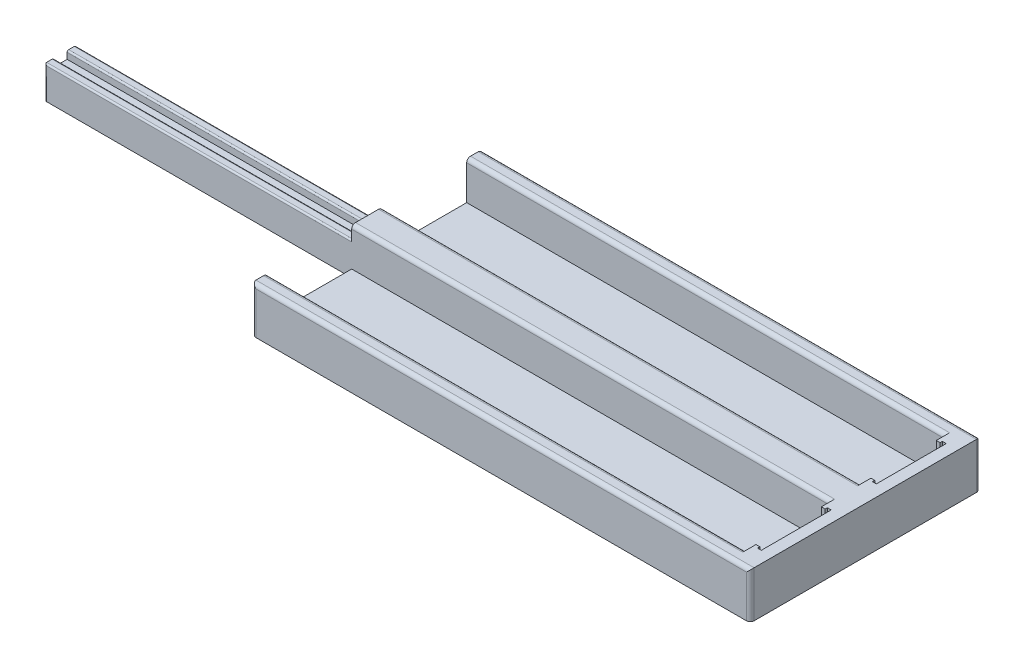
SolidWorks part; units mm, degrees
note: The reader was unsure of these and kept them because the rebuilt part matched: shared geometry of "Sketch3<3>".
ref_plane "Front Plane" through (0, 0, 0) normal (0, 0, 1) x (1, 0, 0)
ref_plane "Top Plane" through (0, 0, 0) normal (0, 1, 0) x (1, 0, 0)
ref_plane "Right Plane" through (0, 0, 0) normal (1, 0, 0) x (0, 0, -1)
sketch "Sketch1" plane through (0, 0, 0) normal (0, 1, 0) x (1, 0, 0)
  line L1 (-65, 30) -> (65, 30)
  line L2 (-65, 30) -> (-65, -30)
  line L3 (-65, -30) -> (65, -30)
  line L4 (65, 30) -> (65, -30)
  line L5 (-65, 30) -> (65, -30) construction
  line L6 (-65, -30) -> (65, 30) construction
  point P0 (0, 0)
  dimension "D1" = 130
  dimension "D2" = 60
extrude "Boss-Extrude1" add sketch "Sketch1" along normal blind 12
ref_plane "Plane2" through (60, 0, 0) normal (1, 0, 0) x (0, 0, -1)
sketch "Sketch2" plane through (65, 0, 0) normal (1, 0, 0) x (0, 0, -1)
  line L0 (0, 0) -> (0, 12) construction
  line L1 (30, 0) -> (-30, 0)
  line L2 (30, 0) -> (30, 12)
  line L3 (30, 12) -> (-30, 12)
  line L4 (-30, 0) -> (-30, 12)
  line L5 (30, 0) -> (-30, 12) construction
  line L6 (30, 12) -> (-30, 0) construction
  line L8 (4, 12) -> (26, 12)
  line L9 (4, 12) -> (4, 2)
  line L10 (4, 2) -> (26, 2)
  line L11 (26, 12) -> (26, 2)
  line L12 (4, 12) -> (26, 2) construction
  line L13 (4, 2) -> (26, 12) construction
  point P4 (0, 6)
  point P14 (15, 7)
  dimension "D1" = 4
  dimension "D2" = 4
  dimension "D3" = 10
extrude "Cut-Extrude1" cut sketch "Sketch2" against normal through all from surface at -5 contours L11 L3 L9 L10 starting at plane "Plane2"
ref_plane "Plane1" through (0, 0, 0) normal (0, 0, 1) x (1, 0, 0)
mirror "Mirror1" about plane through (0, 0, 0) normal (0, 0, 1) of "Cut-Extrude1"
sketch "Sketch3" plane through (60, 0, 0) normal (-1, 0, 0) x (0, 0, 1)
  line L0 (26, 12) -> (4, 12) construction
  line L1 (5.875, 12) -> (24.125, 12)
  line L2 (5.875, 12) -> (5.875, 3)
  line L3 (5.875, 3) -> (24.125, 3)
  line L4 (24.125, 12) -> (24.125, 3)
  line L5 (5.875, 12) -> (24.125, 3) construction
  line L6 (5.875, 3) -> (24.125, 12) construction
  line L7 (15, 7) -> (15, 12) construction
  line L8 (24.125, 12) -> (23.525, 12)
  line L9 (24.125, 12) -> (24.125, 3)
  line L10 (24.125, 3) -> (23.525, 3)
  line L11 (23.525, 12) -> (23.525, 3)
  line L12 (24.125, 12) -> (23.525, 3) construction
  line L13 (24.125, 3) -> (23.525, 12) construction
  line L14 (5.875, 12) -> (6.475, 12)
  line L15 (5.875, 12) -> (5.875, 3)
  line L16 (5.875, 3) -> (6.475, 3)
  line L17 (6.475, 12) -> (6.475, 3)
  line L18 (5.875, 12) -> (6.475, 3) construction
  line L19 (5.875, 3) -> (6.475, 12) construction
  line L20 (5.875, 3) -> (24.125, 3)
  line L21 (5.875, 3) -> (5.875, 3.6)
  line L22 (5.875, 3.6) -> (24.125, 3.6)
  line L23 (24.125, 3) -> (24.125, 3.6)
  line L24 (5.875, 3) -> (24.125, 3.6) construction
  line L25 (5.875, 3.6) -> (24.125, 3) construction
  line L26 (26, 2) -> (4, 2)
  line L27 (26, 2) -> (26, 12) construction
  line L28 (26, 12) -> (4, 12)
  line L29 (4, 2) -> (4, 12) construction
  line L30 (26, 2) -> (4, 12) construction
  line L31 (26, 12) -> (4, 2) construction
  point P4 (15, 7.5)
  point P9 (23.825, 7.5)
  point P12 (6.175, 7.5)
  point P15 (15, 3.3)
  point P20 (15, 7)
  line M12 (26, 12) -> (4, 12)
  dimension "D1" = 18.25
  dimension "D2" = 9
  dimension "D3" = 0.6
  dimension "D4" = 0.6
  dimension "D5" = 0.6
ref_plane "Plane3" through (62, 0, 0) normal (-1, 0, 0) x (0, 0, 1)
extrude "Cut-Extrude2" cut sketch "Sketch3" along normal blind 1 from surface at -2 contours L11 L22 L4 M12 | L22 L11 L3 L9 | L17 L22 L11 L1 | L22 L17 L3 L11 | L22 L15 L3 L17 | L2 L22 L17 M12 starting at plane "Plane3"
extrude "Cut-Extrude3" cut sketch "Sketch3<3>" along normal blind 2 from surface at -2 contours L17 L22 L11 L1 starting at plane "Plane3"
sketch "Sketch3<3>" plane through (60, 0, 0) normal (-1, 0, 0) x (0, 0, 1) same geometry as "Sketch3"
mirror "Mirror2" about plane through (0, 0, 0) normal (0, 0, 1) of "Cut-Extrude3", "Cut-Extrude2"
sketch "Sketch4" plane through (-65, 0, 0) normal (-1, 0, 0) x (0, 0, 1)
  line L0 (-30, 0) -> (30, 0) construction
  line L1 (4, 8.5) -> (-4, 8.5)
  line L2 (4, 8.5) -> (4, 0)
  line L3 (4, 0) -> (-4, 0)
  line L4 (-4, 8.5) -> (-4, 0)
  line L5 (4, 8.5) -> (-4, 0) construction
  line L6 (4, 0) -> (-4, 8.5) construction
  line L7 (-4, 12) -> (-4, 2) construction
  line L9 (4, 12) -> (4, 2) construction
  line L10 (0, 0) -> (0, 8.5) construction
  line L11 (1.75, 8.5) -> (-1.75, 8.5)
  line L12 (1.75, 8.5) -> (1.75, 6.5)
  line L13 (1.75, 6.5) -> (-1.75, 6.5)
  line L14 (-1.75, 8.5) -> (-1.75, 6.5)
  line L15 (1.75, 8.5) -> (-1.75, 6.5) construction
  line L16 (1.75, 6.5) -> (-1.75, 8.5) construction
  point P4 (0, 4.25)
  point P16 (0, 7.5)
  point P17 (0, 0)
  line M8 (4, 2) -> (4, 12)
  line M10 (-4, 12) -> (-4, 2)
  line M15 (-30, 0) -> (30, 0)
  dimension "D1" = 8.5
  dimension "D2" = 2
  dimension "D3" = 3.5
extrude "Boss-Extrude2" add sketch "Sketch4" along normal blind 80 contours L14 L1 L4 L2 L12 L13 M10 M15 M8
fillet "Fillet1" radius 0.4 6 edges at (-105, 8.5, -1.75) (-105, 8.5, 1.75) (-145, 4.25, -4) (-145, 4.25, 4) (-105, 8.5, -4) (-105, 8.5, 4)
fillet "Fillet2" radius 1 10 edges at (-2.5, 12, 4) (0, 12, 30) (-2.5, 12, 26) (-2.5, 12, -26) (0, 12, -30) (-2.5, 12, -4) (-65, 6, 30) (-65, 6, -30) (65, 6, 30) (65, 6, -30)
